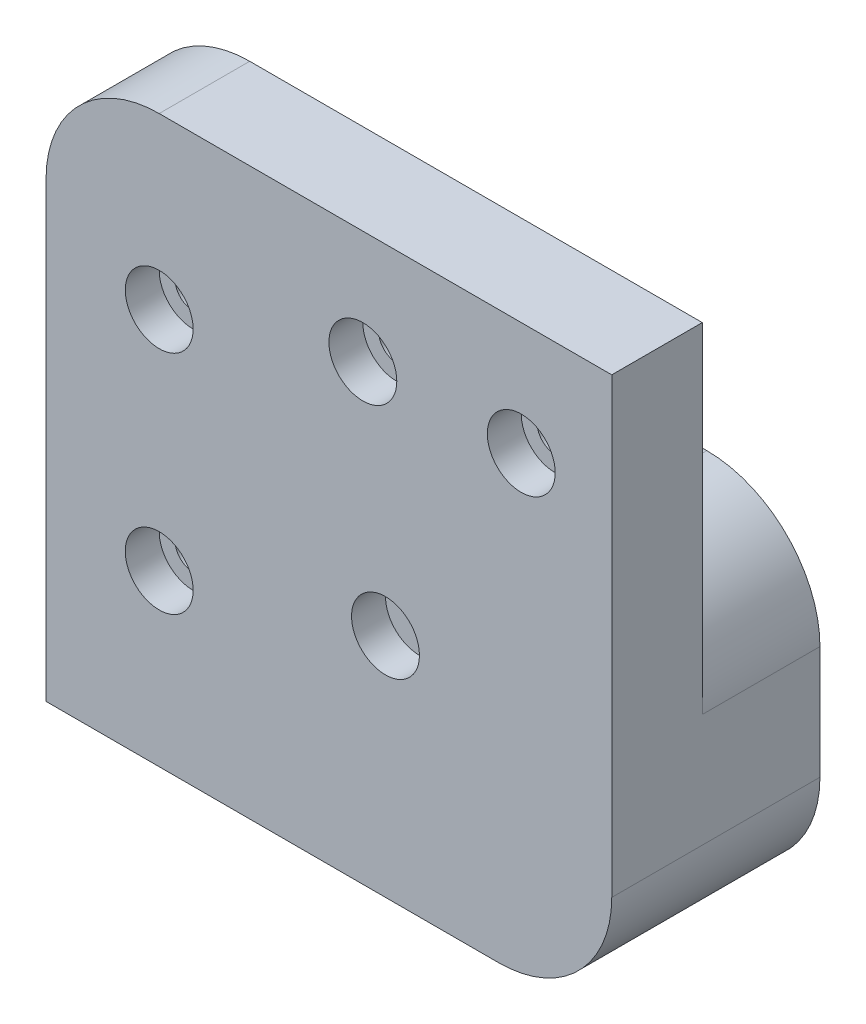
SolidWorks part; units mm, degrees
ref_plane "前视基准面" through (0, 0, 0) normal (0, 0, 1) x (1, 0, 0)
ref_plane "上视基准面" through (0, 0, 0) normal (0, 1, 0) x (1, 0, 0)
ref_plane "右视基准面" through (0, 0, 0) normal (1, 0, 0) x (0, 0, -1)
other "Configuration Table"
sketch "草图1" plane through (0, 0, 0) normal (0, 0, 1) x (1, 0, 0)
  line L0 (-10, 77.5) -> (-10, -160) construction
  line L2 (10, 57.5) -> (10, 27.5)
  line L3 (10, 27.5) -> (-10, 27.5)
  line L4 (-10, 77.5) -> (-10, 27.5)
  line L5 (-10, 77.5) -> (40, 77.5)
  line L7 (10, 57.5) -> (40, 57.5)
  line L8 (40, 77.5) -> (40, 57.5)
  line L9 (184.3942, 77.5) -> (10.0042, 77.5) construction
  line L10 (184.3942, 57.5) -> (10.0042, 57.5) construction
  line L11 (10, -130.0288) -> (10, 47.5288) construction
  circle A0 centre (32, 67.5) radius 1.6
  circle A1 centre (18, 67.5) radius 1.6
  circle A2 centre (0, 62.5) radius 1.6
  circle A3 centre (0, 42.5) radius 1.6
  point P22 (0, 27.5)
  point P23 (40, 67.5)
  dimension "D2" = 3.2
  dimension "D1" = 50
  dimension "D3" = 8
  dimension "D4" = 8
  dimension "D5" = 15
  dimension "D6" = 15
extrude "凸台-拉伸1" add sketch "草图1" along normal blind 8
sketch "草图2" plane through (0, 0, 8) normal (0, 0, 1) x (1, 0, 0)
  circle A0 centre (32, 67.5) radius 3
  circle A1 centre (0, 42.5) radius 1.6
  circle A2 centre (0, 42.5) radius 1.6 construction
  circle A3 centre (0, 62.5) radius 1.6
  circle A4 centre (0, 62.5) radius 1.6 construction
  circle A5 centre (18, 67.5) radius 1.6
  circle A6 centre (18, 67.5) radius 1.6 construction
  circle A7 centre (32, 67.5) radius 1.6
  circle A8 centre (32, 67.5) radius 1.6 construction
  circle A9 centre (18, 67.5) radius 3
  circle A10 centre (0, 62.5) radius 3
  circle A11 centre (0, 42.5) radius 3
  dimension "D1" = 6
  dimension "D2" = 0
  dimension "D3" = 0
  dimension "D4" = 0
  dimension "D5" = 0
extrude "切除-拉伸1" cut sketch "草图2" against normal blind 3
fillet "圆角1" radius 10 2 edges at (10, 57.5, 4) (-10, 77.5, 4)
sketch "草图3" plane through (0, 0, 8) normal (0, 0, 1) x (1, 0, 0)
  line L0 (40, 57.5) -> (40, 27.5)
  line L2 (40, 27.5) -> (10, 27.5)
  line L3 (10, 27.5) -> (10, 47.5) construction
  line L4 (20, 57.5) -> (40, 57.5) construction
  line L5 (10, 27.5) -> (10, 47.5)
  line L6 (20, 57.5) -> (40, 57.5)
  line L7 (-10, 27.5) -> (10, 27.5) construction
  arc A0 (20, -92.5173) -> (10, -102.5173) centre (20, -102.5173) ccw construction
  arc A1 (20, -92.5173) -> (10, -102.5173) centre (20, -102.5173) ccw
  circle A2 centre (20, -102.5173) radius 2.05 construction
  circle A3 centre (20, -102.5173) radius 2.05 construction
  circle A4 centre (20, -102.5173) radius 1.6
  line M10 (10, 27.5) -> (10, 47.5)
  arc M11 (10, 47.5) -> (20, 57.5) centre (20, 47.5) cw
  line M12 (20, 57.5) -> (40, 57.5)
  dimension "D1" = 3.2
extrude "凸台-拉伸2" add sketch "草图3" against normal up to surface (18.3999 mm away) contours L2 L0 M12 M11 M10 region at (25.3118, 42.1882, 8)
sketch "草图5" plane through (0, 0, 8) normal (0, 0, 1) x (1, 0, 0)
  circle A0 centre (20, 47.5288) radius 1.6 construction
  circle A1 centre (20, 47.5288) radius 1.6 construction
  circle A2 centre (20, 47.5288) radius 3
  dimension "D1" = 6
extrude "切除-拉伸2" cut sketch "草图5" against normal blind 3
fillet "圆角2" radius 10 3 edges at (10, 27.5, -5.2) (40, 57.5, -5.2) (40, 27.5, -1.2)
